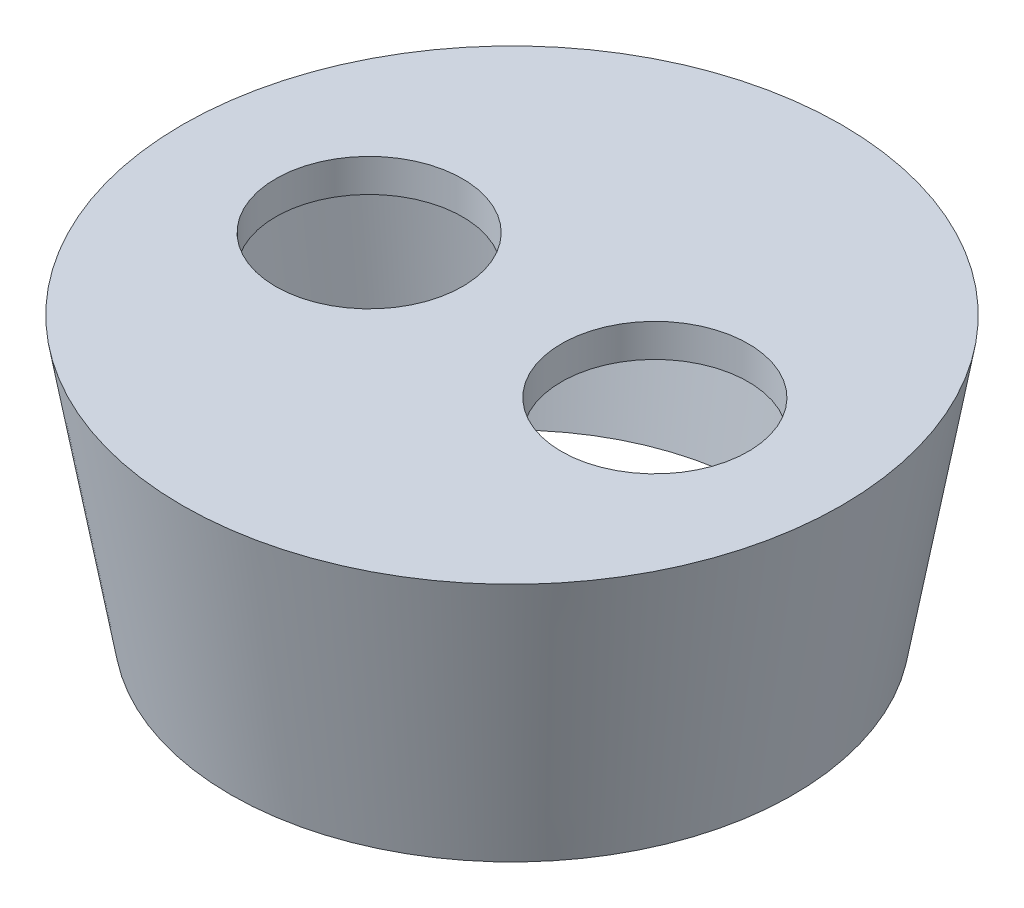
SolidWorks part; units mm, degrees
ref_plane "Front Plane" through (0, 0, 0) normal (0, 0, 1) x (1, 0, 0)
ref_plane "Top Plane" through (0, 0, 0) normal (0, 1, 0) x (1, 0, 0)
ref_plane "Right Plane" through (0, 0, 0) normal (1, 0, 0) x (0, 0, -1)
sketch "Sketch1" plane through (0, 0, 0) normal (0, 1, 0) x (1, 0, 0)
  line L0 (0, 27.7018) -> (0, -29.8031) construction
  line L2 (-22.5, 10) -> (22.5, 10)
  line L3 (-22.5, 10) -> (-22.5, -10)
  line L4 (-22.5, -10) -> (22.5, -10)
  line L5 (22.5, 10) -> (22.5, -10)
  line L6 (-22.5, 10) -> (22.5, -10) construction
  line L7 (-22.5, -10) -> (22.5, 10) construction
  circle A0 centre (0, 0) radius 30
  circle A1 centre (-13, 0) radius 8.5
  circle A2 centre (13, 0) radius 8.5
  dimension "D1" = 60
  dimension "D2" = 17
  dimension "D3" = 20
  dimension "D4" = 26
  dimension "D5" = 26
  dimension "D6" = 45
extrude "Boss-Extrude1" add sketch "Sketch1" against normal blind 25 contours A0
draft "Draft1" type of draft neutral plane draft angle 10 faces to draft 1 face at (0, -25, 30) neutral plane through (0, 0, 0) neutral plane normal (0, 1, 0) reverse direction yes parameters "D1"=10
shell "Shell2" thickness 3 removed face at (0, -25, 25.5918)
extrude "Cut-Extrude2" cut sketch "Sketch1<4>" against normal up to surface (3 mm away) contours A1 | A2 up to face at (0, -3, 26.4247)
sketch "Sketch1<4>" plane through (0, 0, 0) normal (0, 1, 0) x (1, 0, 0) same geometry as "Sketch1"
